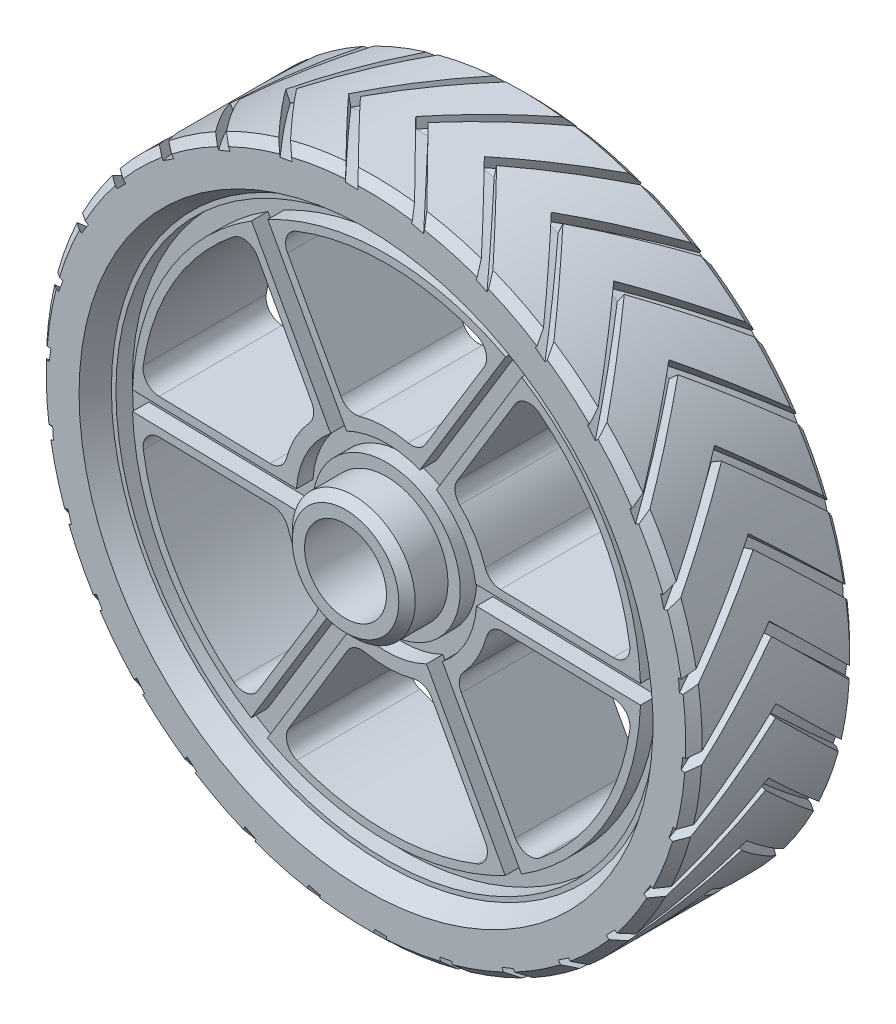
SolidWorks part; units mm, degrees
note: The reader was unsure of these and kept them because the rebuilt part matched: shared geometry of "Sketch8<2>".
material "Alloy Steel"
ref_plane "Front Plane" through (0, 0, 0) normal (0, 0, 1) x (1, 0, 0)
ref_plane "Top Plane" through (0, 0, 0) normal (0, 1, 0) x (1, 0, 0)
ref_plane "Right Plane" through (0, 0, 0) normal (1, 0, 0) x (0, 0, -1)
sketch "Sketch1" plane through (0, 0, 0) normal (0, 0, 1) x (1, 0, 0)
  circle A0 centre (0, 0) radius 40
  dimension "D1" = 80
extrude "Boss-Extrude1" add sketch "Sketch1" along normal mid plane 20
sketch "Sketch2" plane through (0, 0, -10) normal (0, 0, -1) x (-1, 0, 0)
  circle A0 centre (0, 0) radius 35
  dimension "D1" = 70
extrude "Cut-Extrude1" cut sketch "Sketch2" against normal blind 2.5 draft 30
mirror "Mirror1" about plane through (0, 0, 0) normal (0, 0, 1) of "Cut-Extrude1"
sketch "Sketch3" plane through (0, 0, -7.5) normal (0, 0, -1) x (-1, 0, 0)
  line L0 (-4.768, 13.2907) -> (-11.916, 25.0331)
  line L1 (0, 30) -> (0, 30) construction
  line L2 (5.5619, 13.191) -> (12.06, 25.0751)
  circle A0 centre (0, 0) radius 30 construction
  circle A1 centre (0, 0) radius 30 construction
  arc A2 (-10.9368, 27.9354) -> (11.0413, 27.8943) centre (0, 0) cw
  arc A3 (-2.642, 12.3748) -> (3.2874, 12.2192) centre (0, 0) cw
  arc A4 (-10.9368, 27.9354) -> (-11.916, 25.0331) centre (-10.2077, 26.073) ccw
  arc A5 (11.0413, 27.8943) -> (12.06, 25.0751) centre (10.3052, 26.0346) cw
  arc A6 (5.5619, 13.191) -> (3.2874, 12.2192) centre (3.8071, 14.1505) cw
  arc A7 (-2.642, 12.3748) -> (-4.768, 13.2907) centre (-3.0596, 14.3307) cw
  point P16 (-13.105, 26.9863)
  point P19 (13.105, 26.9863)
  point P22 (7.105, 16.594)
  point P25 (-7.105, 16.594)
  dimension "D1" = 60
  dimension "D2" = 60
  dimension "D3" = 60
  dimension "D5" = 2
extrude "Cut-Extrude2" cut sketch "Sketch3" against normal up to next
pattern_circular "CirPattern1" count 6 over 360 about axis through (0, 0, 0) along (0, 0, 1) of "Cut-Extrude2"
sketch "Sketch4" plane through (0, 0, -7.5) normal (0, 0, -1) x (-1, 0, 0)
  circle A0 centre (0, 0) radius 5
  circle A1 centre (0, 0) radius 7.5
  dimension "D1" = 10
  dimension "D2" = 15
extrude "Boss-Extrude2" add sketch "Sketch4" along normal blind 5
mirror "Mirror2" about plane through (0, 0, 0) normal (0, 0, 1) of "Boss-Extrude2"
sketch "Sketch5" plane through (0, 0, -7.5) normal (0, 0, -1) x (-1, 0, 0)
  circle A0 centre (0, 0) radius 5
extrude "Cut-Extrude3" cut sketch "Sketch5" against normal up to next
sketch "Sketch6" plane through (0, 0, -7.5) normal (0, 0, -1) x (-1, 0, 0)
  line L0 (-4.0692, 10.2197) -> (-14.5208, 27.3888)
  line L1 (-16.5006, 26.2437) -> (-6.098, 9.155)
  line L2 (-25.9526, 15.0486) -> (-10.7887, 6.6121) construction
  line L3 (-11.1206, -6.0372) -> (-26.0088, -14.9513) construction
  line L4 (11.1206, 6.0372) -> (26.0088, 14.9513) construction
  line L5 (0.332, 12.6493) -> (0.0562, 29.9999) construction
  line L6 (16.459, 26.2698) -> (6.8159, 8.6339)
  line L7 (4.8794, 9.8586) -> (14.4774, 27.4118)
  line L8 (-10.9775, -0.7036) -> (-30.978, -1.1681)
  line L9 (-30.9798, 1.1191) -> (-10.8851, 1.5858)
  line L10 (30.978, 1.1681) -> (10.9775, 0.7036)
  line L11 (10.8851, -1.5858) -> (30.9798, -1.1191)
  line L12 (6.098, -9.155) -> (16.5006, -26.2437)
  line L13 (14.5208, -27.3888) -> (4.0692, -10.2197)
  line L14 (-14.4774, -27.4118) -> (-4.8794, -9.8586)
  line L15 (-6.8159, -8.6339) -> (-16.459, -26.2698)
  line L16 (11.916, -25.0331) -> (4.768, -13.2907) construction
  line L17 (8.6428, -11.4122) -> (15.6857, -22.9818) construction
  line L18 (-5.5619, -13.191) -> (-12.06, -25.0751) construction
  line L19 (14.2047, 1.7788) -> (27.7457, 2.0933) construction
  line L20 (27.6373, -2.197) -> (13.8941, -2.5162) construction
  line L21 (-27.6373, 2.197) -> (-13.8941, 2.5162) construction
  line L22 (-14.2047, -1.7788) -> (-27.7457, -2.0933) construction
  line L23 (15.7213, 22.8361) -> (9.1261, 10.7746) construction
  line L24 (5.5619, 13.191) -> (12.06, 25.0751) construction
  line L25 (-11.916, 25.0331) -> (-4.768, 13.2907) construction
  line L26 (-8.6428, 11.4122) -> (-15.6857, 22.9818) construction
  line L27 (-15.7213, -22.8361) -> (-9.1261, -10.7746) construction
  arc A0 (-18.6365, 23.5092) -> (-29.6612, 4.4962) centre (0, 0) ccw construction
  arc A1 (-8.9384, 8.9566) -> (-12.0379, 3.8993) centre (0, 0) ccw construction
  arc A2 (-12.2258, -3.2626) -> (-9.3959, -8.4755) centre (0, 0) ccw construction
  arc A3 (-29.6778, -4.3851) -> (-18.7244, -23.4392) centre (0, 0) ccw construction
  arc A4 (12.2258, 3.2626) -> (9.3959, 8.4755) centre (0, 0) ccw construction
  arc A5 (29.6778, 4.3851) -> (18.7244, 23.4392) centre (0, 0) ccw construction
  arc A6 (3.2874, 12.2192) -> (-2.642, 12.3748) centre (0, 0) ccw construction
  arc A7 (11.0413, 27.8943) -> (-10.9368, 27.9354) centre (0, 0) ccw construction
  circle A8 centre (0, 0) radius 9
  arc A9 (-6.098, 9.155) -> (-10.8851, 1.5858) centre (0, 0) ccw
  arc A10 (4.8794, 9.8586) -> (-4.0692, 10.2197) centre (0, 0) ccw
  arc A11 (10.9775, 0.7036) -> (6.8159, 8.6339) centre (0, 0) ccw
  arc A12 (6.098, -9.155) -> (10.8851, -1.5858) centre (0, 0) ccw
  arc A13 (-4.8794, -9.8586) -> (4.0692, -10.2197) centre (0, 0) ccw
  arc A14 (-10.9775, -0.7036) -> (-6.8159, -8.6339) centre (0, 0) ccw
  circle A15 centre (0, 0) radius 33
  arc A16 (14.4774, 27.4118) -> (-14.5208, 27.3888) centre (0, 0) ccw
  arc A17 (30.978, 1.1681) -> (16.459, 26.2698) centre (0, 0) ccw
  arc A18 (16.5006, -26.2437) -> (30.9798, -1.1191) centre (0, 0) ccw
  arc A19 (-14.4774, -27.4118) -> (14.5208, -27.3888) centre (0, 0) ccw
  arc A20 (-30.978, -1.1681) -> (-16.459, -26.2698) centre (0, 0) ccw
  arc A21 (-16.5006, 26.2437) -> (-30.9798, 1.1191) centre (0, 0) ccw
  dimension "D1" = 18
  dimension "D2" = 22
  dimension "D15" = 66
  dimension "D16" = 62
  dimension "D3" = 1
  dimension "D4" = 1
  dimension "D5" = 1
  dimension "D6" = 1
  dimension "D7" = 1
  dimension "D8" = 1
  dimension "D9" = 1
  dimension "D10" = 1
  dimension "D11" = 1
  dimension "D12" = 1
  dimension "D13" = 1
  dimension "D14" = 1
extrude "Cut-Extrude4" cut sketch "Sketch6" against normal blind 2
mirror "Mirror3" about plane through (0, 0, 0) normal (0, 0, 1) of "Cut-Extrude4"
chamfer "Chamfer1" distance 1 angle 45 2 edges at (-7.5, 0, -12.5) (-7.5, 0, 12.5)
chamfer "Chamfer2" distance 1 angle 45 2 edges at (40, 0, -10) (40, 0, 10)
sketch "Sketch7" plane through (0, 0, 0) normal (0, 0, 1) x (1, 0, 0)
  circle A0 centre (0, 0) radius 40
  dimension "D1" = 80
curve "Helix/Spiral1" pitch 255 height 13 radius 40 left hand yes centre (0, 0, 0) axis (0, 0, 1) start towards (-0.5446, 0.8387, 0)
sketch "Sketch8" plane through (0, 0, 0) normal (0, 0, 1) x (1, 0, 0)
  line L1 (-3.931, 38.4733) -> (-2.431, 38.4733)
  line L2 (-3.931, 38.4733) -> (-3.931, 41.2733)
  line L3 (-3.931, 41.2733) -> (-2.431, 41.2733)
  line L4 (-2.431, 38.4733) -> (-2.431, 41.2733)
  line L5 (-3.931, 38.4733) -> (-2.431, 41.2733) construction
  line L6 (-3.931, 41.2733) -> (-2.431, 38.4733) construction
  circle A0 centre (0, 0) radius 40 construction
  point P0 (-3.181, 39.8733)
  dimension "D1" = 2.8
  dimension "D2" = 1.5
sweep "Cut-Sweep1" cut profiles "Sketch8" path "Helix/Spiral1" align with end faces yes
sketch "Sketch10" plane through (0, 0, 0) normal (0, 0, 1) x (1, 0, 0)
  circle A1 centre (0, 0) radius 40
  circle A2 centre (0, 0) radius 40
  dimension "D1" = 0
curve "Helix/Spiral2" pitch 255 height 13 turns 0.051
sweep "Cut-Sweep2" cut profiles "Sketch8<2>" path "Helix/Spiral2" align with end faces yes
sketch "Sketch8<2>" plane through (0, 0, 0) normal (0, 0, 1) x (1, 0, 0) same geometry as "Sketch8"
pattern_circular "CirPattern2" count 30 over 360 about axis through (0, 0, 9) along (0, 0, 1) of "Cut-Sweep2", "Cut-Sweep1"
